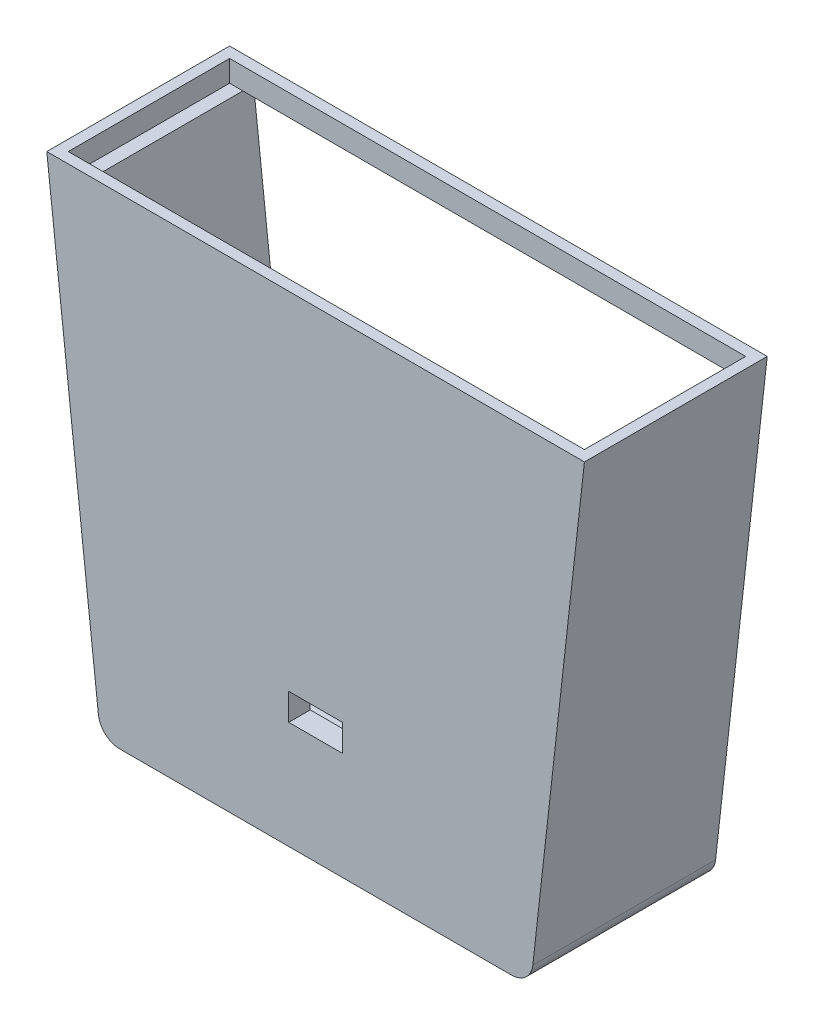
SolidWorks part; units mm, degrees
ref_plane "Front Plane" through (0, 0, 0) normal (0, 0, 1) x (1, 0, 0)
ref_plane "Top Plane" through (0, 0, 0) normal (0, 1, 0) x (1, 0, 0)
ref_plane "Right Plane" through (0, 0, 0) normal (1, 0, 0) x (0, 0, -1)
sketch "Sketch1" plane through (0, 0, 0) normal (0, 0, 1) x (1, 0, 0)
  line L0 (0, 56.7961) -> (0, -56.7961) construction
  line L1 (63.5, 56.7961) -> (-63.5, 56.7961)
  line L2 (-63.5, 56.7961) -> (-51.3049, -52.2806)
  line L3 (-46.2563, -56.7961) -> (46.2563, -56.7961)
  line L4 (63.5, 56.7961) -> (51.3049, -52.2806)
  line L5 (6.35, -25.0461) -> (-6.35, -25.0461)
  line L6 (-6.35, -25.0461) -> (-6.35, -31.3961)
  line L7 (-6.35, -31.3961) -> (6.35, -31.3961)
  line L8 (6.35, -25.0461) -> (6.35, -31.3961)
  arc A0 (-51.3049, -52.2806) -> (-46.2563, -56.7961) centre (-46.2563, -51.7161) ccw
  arc A1 (51.3049, -52.2806) -> (46.2563, -56.7961) centre (46.2563, -51.7161) cw
  point P10 (-50.8, -56.7961)
  point P16 (0, -31.3961)
  point P18 (0, -25.0461)
  dimension "D4" = 5.08
  dimension "D6" = 6.35
  dimension "D7" = 6.35
  dimension "D8" = 25.4
  dimension "D1" = 50.8
  dimension "D2" = 63.5
  dimension "D3" = 56.7961
  dimension "D5" = 109.0767
extrude "Boss-Extrude1" add sketch "Sketch1" against normal blind 5.08
sketch "Sketch2" plane through (0, 0, -5.08) normal (0, 0, 1) x (1, 0, 0)
  line L0 (0, 56.7961) -> (0, -56.7961) construction
  line L1 (63.5, 56.7961) -> (-63.5, 56.7961)
  line L2 (-63.5, 56.7961) -> (-51.3049, -52.2806)
  line L3 (-46.2563, -56.7961) -> (46.2563, -56.7961)
  line L4 (63.5, 56.7961) -> (51.3049, -52.2806)
  line L5 (6.35, -25.0461) -> (-6.35, -25.0461)
  line L6 (-6.35, -25.0461) -> (-6.35, -31.3961)
  line L7 (-6.35, -31.3961) -> (6.35, -31.3961)
  line L8 (6.35, -25.0461) -> (6.35, -31.3961)
  line L9 (-6.35, -25.0461) -> (-6.35, -31.3961) construction
  line L10 (6.35, -25.0461) -> (-6.35, -25.0461) construction
  line L11 (-57.8204, 51.7161) -> (57.8204, 51.7161)
  line L12 (57.8204, 51.7161) -> (46.7612, -47.2006)
  line L13 (41.7126, -51.7161) -> (-41.7126, -51.7161)
  line L14 (-57.8204, 51.7161) -> (-46.7612, -47.2006)
  arc A0 (-51.3049, -52.2806) -> (-46.2563, -56.7961) centre (-46.2563, -51.7161) ccw
  arc A1 (51.3049, -52.2806) -> (46.2563, -56.7961) centre (46.2563, -51.7161) cw
  arc A2 (46.7612, -47.2006) -> (41.7126, -51.7161) centre (41.7126, -46.6361) cw
  arc A3 (-46.7612, -47.2006) -> (-41.7126, -51.7161) centre (-41.7126, -46.6361) ccw
  point P10 (-50.8, -56.7961)
  point P16 (0, -31.3961)
  point P18 (0, -25.0461)
  point P30 (0, -51.7161)
  point P33 (0, 51.7161)
  arc M18 (51.3049, -52.2806) -> (46.2563, -56.7961) centre (46.2563, -51.7161) cw
  line M19 (46.2563, -56.7961) -> (-46.2563, -56.7961)
  arc M20 (-46.2563, -56.7961) -> (-51.3049, -52.2806) centre (-46.2563, -51.7161) cw
  line M21 (-51.3049, -52.2806) -> (-63.5, 56.7961)
  line M22 (-63.5, 56.7961) -> (63.5, 56.7961)
  line M23 (63.5, 56.7961) -> (51.3049, -52.2806)
  dimension "D4" = 5.08
  dimension "D6" = 6.35
  dimension "D7" = 6.35
  dimension "D8" = 25.4
  dimension "D9" = 0
  dimension "D10" = 5.08
  dimension "D1" = 50.8
  dimension "D2" = 63.5
  dimension "D3" = 5.08
  dimension "D5" = 109.0767
extrude "Boss-Extrude2" add sketch "Sketch2" against normal blind 38.1 contours L0 L1 L13 A2 L12 L11 M23 M18 M19 | L0 L11 L14 A3 L13 L3 M22 M20 M21 region at (31.75, 55.4948, -5.08) region at (-1.3014, 54.2561, -5.08)
sketch "Sketch4" plane through (0, 56.7961, -56.7961) normal (0, -1, 0) x (1, 0, 0)
  line L0 (60.96, 16.1561) -> (60.96, 54.2561)
  line L1 (60.96, 16.1561) -> (-60.96, 16.1561)
  line L2 (60.96, 54.2561) -> (-60.96, 54.2561)
  line L3 (-60.96, 16.1561) -> (-60.96, 54.2561)
  line L4 (63.5, 56.7961) -> (-63.5, 56.7961) construction
  line L5 (-63.5, 13.6161) -> (-63.5, 56.7961) construction
  line L6 (63.5, 13.6161) -> (63.5, 56.7961) construction
  line L7 (-63.5, 13.6161) -> (63.5, 13.6161) construction
  dimension "D1" = 2.54
  dimension "D2" = 2.54
  dimension "D3" = 2.54
  dimension "D4" = 2.54
extrude "Cut-Extrude1" cut sketch "Sketch4" along normal blind 5.08
sketch "Sketch6" plane through (0, 0, -43.18) normal (0, 0, 1) x (1, 0, 0)
  line L0 (0, 50.5747) -> (0, -51.7161) construction
  line L3 (-52.9958, 8.564) -> (-33.9458, 8.564)
  line L5 (-33.9458, 8.564) -> (-33.9458, -4.136)
  line L6 (-33.9458, -4.136) -> (-51.5759, -4.136)
  line L8 (33.9458, -4.136) -> (51.5759, -4.136)
  line L9 (33.9458, 8.564) -> (33.9458, -4.136)
  line L10 (52.9958, 8.564) -> (33.9458, 8.564)
  line L11 (-51.5759, -4.136) -> (-52.9958, 8.564)
  line L12 (52.9958, 8.564) -> (51.5759, -4.136)
  line L13 (-57.8204, 51.7161) -> (57.8204, 51.7161) construction
  dimension "D1" = 19.05
  dimension "D2" = 12.7
  dimension "D3" = 33.9458
  dimension "D4" = 4.8246
  dimension "D5" = 6.2445
  dimension "D6" = 43.1521
extrude "Boss-Extrude3" add sketch "Sketch6" along normal blind 2.54
sketch "Sketch7" plane through (0, 0, -43.18) normal (0, 0, 1) x (1, 0, 0)
  line L0 (-43.4708, 8.564) -> (-42.7609, -4.136) construction
  line L1 (-63.5, 56.7961) -> (63.5, 56.7961) construction
  line L2 (-51.5759, -4.136) -> (-33.9458, -4.136) construction
  line L3 (0, 56.7961) -> (0, -51.7161) construction
  line L4 (-33.9458, 8.564) -> (-52.9958, 8.564) construction
  line L6 (-33.9458, -4.136) -> (-33.9458, 8.564) construction
  line L7 (-57.8204, 51.7161) -> (57.8204, 51.7161) construction
  circle A0 centre (-43.1159, 2.214) radius 1.905
  circle A2 centre (43.1159, 2.214) radius 1.905
  dimension "D1" = 3.81
extrude "Cut-Extrude2" cut sketch "Sketch7" along normal blind 2.54
sketch "Sketch8" plane through (0, 0, -5.08) normal (0, 0, -1) x (-1, 0, 0)
  line L0 (0, 51.7161) -> (0, -51.7161) construction
  line L1 (57.8204, 51.7161) -> (-57.8204, 51.7161) construction
  line L2 (-41.7126, -51.7161) -> (41.7126, -51.7161) construction
  line L4 (-25.085, 41.5561) -> (-25.085, -20.9787)
  line L5 (-25.085, -20.9787) -> (25.085, -20.9787)
  line L7 (-25.085, 41.5561) -> (25.085, -20.9787)
  point P11 (0, -20.9787)
  dimension "D1" = 50.1701
  dimension "D2" = 62.5348
  dimension "D3" = 10.16
extrude "Boss-Extrude4" add sketch "Sketch8" along normal blind 9.017
ref_plane "Plane1" through (0, 0, -11.557) normal (0, 0, -1) x (-1, 0, 0)
sketch "Sketch12" plane through (0, 0, -11.557) normal (0, 0, -1) x (-1, 0, 0)
  line L0 (-22.545, -18.4387) -> (23.0473, -18.4387)
  line L1 (25.085, -20.9787) -> (-25.085, 41.5561) construction
  line L2 (-22.545, -18.4387) -> (-22.545, 38.3901)
  line L3 (-22.545, 38.3901) -> (23.0473, -18.4387)
  line L4 (-25.085, -20.9787) -> (25.085, -20.9787) construction
  line L6 (-25.085, 41.5561) -> (-25.085, -20.9787) construction
  dimension "D1" = 2.54
  dimension "D2" = 2.54
extrude "Cut-Extrude6" cut sketch "Sketch12" against normal blind 6.477
